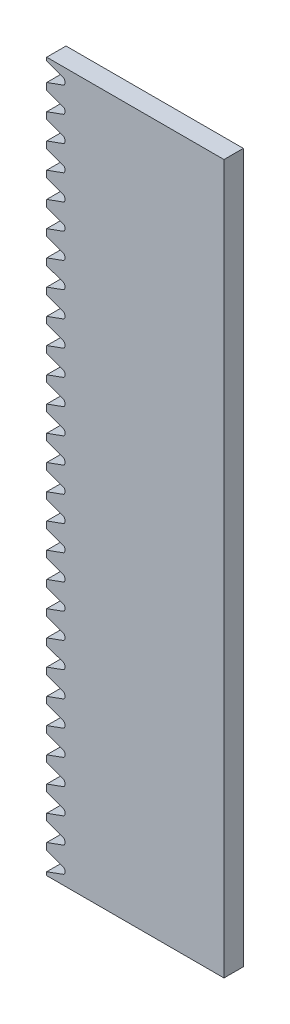
SolidWorks part; units mm, degrees
ref_plane "Front Plane" through (0, 0, 0) normal (0, 0, 1) x (1, 0, 0)
ref_plane "Top Plane" through (0, 0, 0) normal (0, 1, 0) x (1, 0, 0)
ref_plane "Right Plane" through (0, 0, 0) normal (1, 0, 0) x (0, 0, -1)
ref_axis "Axis1" through (0, -55, 0) along (0, 1, 0)
sketch "SketchCI.m_strSketchName" plane through (0, 0, 0) normal (0, 0, 1) x (1, 0, 0)
  line L0 (-1.6667, 2.618) -> (-1.6667, -143.9897)
  line L1 (-1.6667, -143.9897) -> (35, -143.9897)
  line L2 (35, -143.9897) -> (35, 2.618)
  line L3 (35, 2.618) -> (-1.6667, 2.618)
  dimension "D1" = 1.6667
  dimension "D2" = 143.9897
  dimension "D3" = 35
  dimension "D4" = 2.618
extrude "ExtrudeCI" add sketch "SketchCI.m_strSketchName" along normal blind 2 and the other way blind 2
sketch "SketchToothSpurGear2" plane through (0, 0, 0) normal (0, 0, 1) x (1, 0, 0)
  line L0 (-1.6667, 1.9156) -> (-1.6667, -1.9156)
  line L1 (-1.6667, -1.9156) -> (1.7543, -0.6705)
  line L2 (2.0833, -0.2006) -> (2.0833, 0.2006)
  line L3 (1.7543, 0.6705) -> (-1.6667, 1.9156)
  arc A0 (1.7543, -0.6705) -> (2.0833, -0.2006) centre (1.5833, -0.2006) ccw
  arc A1 (2.0833, 0.2006) -> (1.7543, 0.6705) centre (1.5833, 0.2006) ccw
  dimension "D1" = 1
  dimension "D2" = 1
  dimension "ADDENDUM" = 1.6667
  dimension "FLANKONE" = 1.2301
  dimension "FLANKONEANGLE" = 70
  dimension "DEDENDUM" = 2.0833
  dimension "FLANKTWO" = 1.2301
  dimension "FLANKTWOANGLE" = 70
extrude "ToothExtrudeCutSpurGear2" cut sketch "SketchToothSpurGear2" against normal blind 9.525 and the other way blind 9.525
pattern_linear "PatternSpurGear2" count 28 spacing 5.236 along (0, -1, 0) of "ToothExtrudeCutSpurGear2"
sketch "AuxiliarySketchSpurGear2" plane through (0, 0, 0) normal (0, 0, 1) x (1, 0, 0)
  line L0 (0, 0) -> (0, -146.6077) construction
